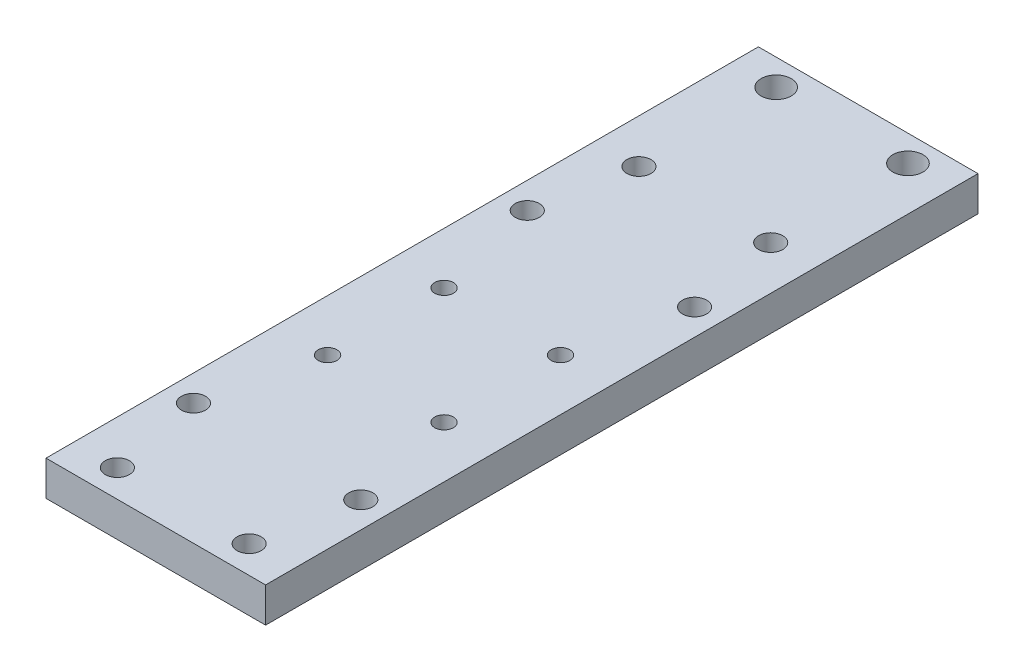
SolidWorks part; units mm, degrees
material "6061 Alloy"
ref_plane "Front Plane" through (0, 0, 0) normal (0, 0, 1) x (1, 0, 0)
ref_plane "Top Plane" through (0, 0, 0) normal (0, 1, 0) x (1, 0, 0)
ref_plane "Right Plane" through (0, 0, 0) normal (1, 0, 0) x (0, 0, -1)
sketch "Sketch1" plane through (0, 0, 0) normal (0, 1, 0) x (1, 0, 0)
  line L1 (-20, 80) -> (20, 80)
  line L2 (-20, 80) -> (-20, -80)
  line L3 (-20, -80) -> (20, -80)
  line L4 (20, 80) -> (20, -80)
  line L5 (0, -80) -> (0, 80) construction
  line L6 (-20, 0) -> (20, 0) construction
  point P0 (0, 0)
  dimension "D1" = 40
  dimension "D2" = 160
extrude "Boss-Extrude1" add sketch "Sketch1" along normal mid plane 6.35
sketch "Sketch3" plane through (0, 0, 0) normal (0, 1, 0) x (1, 0, 0)
  line L0 (0, 75.2375) -> (12, 75.2375) construction
  line L5 (0, -80) -> (0, 80) construction
  line L6 (-20, 0) -> (20, 0) construction
  line L7 (0, 50.2375) -> (12, 50.2375) construction
  line L8 (20, 80) -> (-20, 80) construction
  line L9 (-20, 80) -> (-20, -80) construction
  line L10 (-20, -80) -> (20, -80) construction
  line L11 (20, -80) -> (20, 80) construction
  circle A0 centre (12, 75.2375) radius 2.75
  circle A1 centre (12, 50.2375) radius 2.2
  circle A2 centre (-12, 50.2375) radius 2.2
  circle A3 centre (-12, 75.2375) radius 2.75
  circle A4 centre (-12, -44.7625) radius 2.2
  circle A5 centre (12, -44.7625) radius 2.2
  point P0 (0, 0)
  dimension "D4" = 5.5
  dimension "D5" = 4.4
  dimension "D1" = 4.7625
  dimension "D2" = 25
  dimension "D3" = 12
  dimension "D6" = 2
extrude "M4/5_through" cut sketch "Sketch3" against normal up to surface (3.175 mm away) and the other way blind 6.35 up to face at (0, -3.175, 0)
sketch "Sketch4" plane through (0, 0, -80) normal (0, 0, -1) x (-1, 0, 0)
  circle A0 centre (0, 0) radius 1.3
  dimension "D1" = 2.6
extrude "M3_DRILL" cut sketch "Sketch4" against normal blind 8
sketch "Sketch5" plane through (0, 3.175, 0) normal (0, 1, 0) x (1, 0, 0)
  line L0 (-12, -44.7625) -> (0, -44.7625) construction
  line L2 (0, 0) -> (0, -23.6676) construction
  line L3 (-12, 50.2375) -> (-12, -44.7625) construction
  line L4 (-12, 2.7375) -> (-1.1233, 2.7375) construction
  line L5 (-20, 80) -> (-20, -80) construction
  circle A0 centre (-15.2375, -27.6625) radius 2.2
  circle A1 centre (15.2375, -27.6625) radius 2.2
  circle A2 centre (15.2375, 33.1375) radius 2.2
  circle A3 centre (-15.2375, 33.1375) radius 2.2
  circle A4 centre (-12, -44.7625) radius 2.2 construction
  dimension "D2" = 4.4
  dimension "D1" = 17.1
  dimension "D3" = 4.7625
extrude "M4_through" cut sketch "Sketch5" against normal up to surface (6.35 mm away) up to face at (12, -3.175, 46.9625)
sketch "Sketch6" plane through (0, 0, 0) normal (0, 1, 0) x (1, 0, 0)
  line L0 (0, 2.7375) -> (0, 0) construction
  line L1 (-10.6066, 13.3441) -> (0, 2.7375) construction
  line L2 (-15.2375, 33.1375) -> (-15.2375, -27.6625) construction
  line L3 (-15.2375, 2.7375) -> (0, 2.7375) construction
  circle A0 centre (0, 2.7375) radius 15 construction
  circle A1 centre (-10.6066, 13.3441) radius 1.7
  circle A2 centre (10.6066, 13.3441) radius 1.7
  circle A3 centre (10.6066, -7.8691) radius 1.7
  circle A4 centre (-10.6066, -7.8691) radius 1.7
  point P15 (0, 2.7375)
  dimension "D2" = 30
  dimension "D4" = 3.4
  dimension "D3" = 135
  dimension "D5" = 4
extrude "M4_Drill" cut sketch "Sketch6" along normal up to surface (3.175 mm away) and the other way blind 10 up to face at (-15.2375, 3.175, -35.3375)
sketch "Sketch7" plane through (0, 3.175, 0) normal (0, 1, 0) x (1, 0, 0)
  line L0 (-12, -44.7625) -> (12, -44.7625) construction
  line L1 (20, -80) -> (20, 80) construction
  line L2 (-20, -80) -> (20, -80)
  line L3 (-20, -80) -> (-20, -49.7625)
  line L4 (-20, -49.7625) -> (20, -49.7625)
  line L5 (20, -80) -> (20, -49.7625)
  line L6 (0, -49.7625) -> (0, -80) construction
  line L7 (-20, -64.8812) -> (20, -64.8812) construction
  point P216 (0, -64.8812)
  dimension "D1" = 5
extrude "Cut-Extrude2" cut sketch "Sketch7" against normal up to surface (6.35 mm away) up to face at (-10.6066, -3.175, 9.5691)
